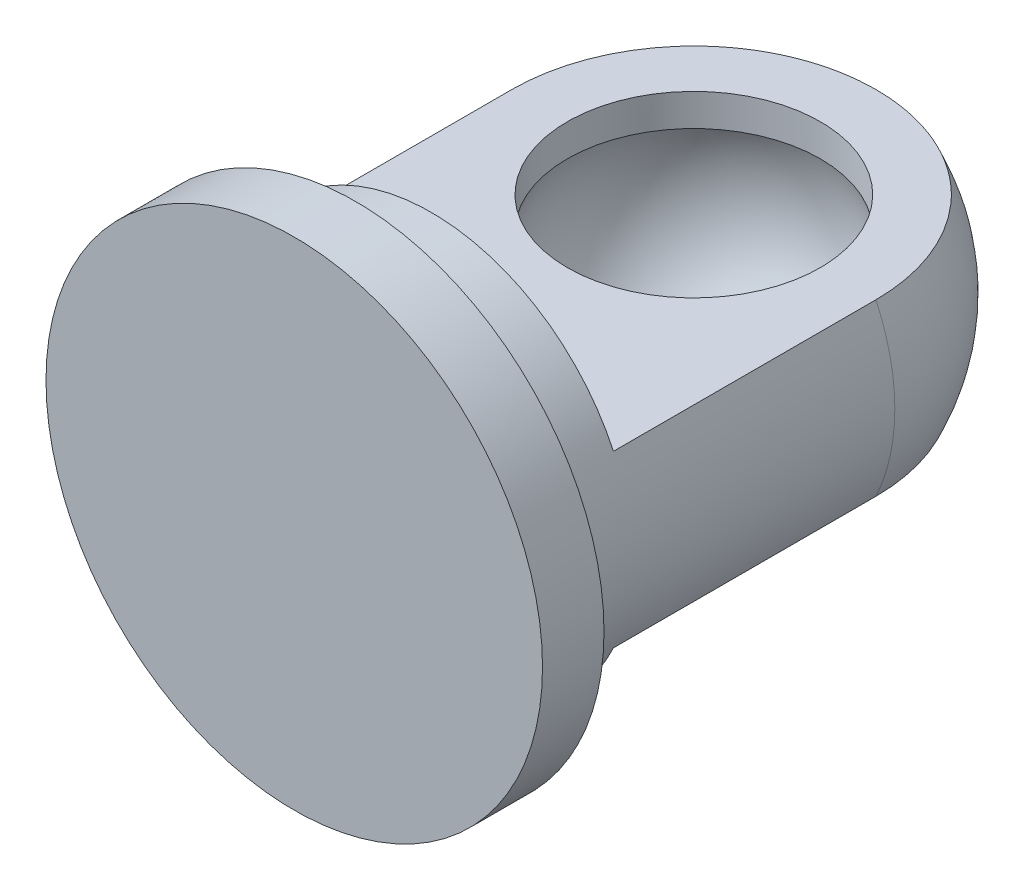
SolidWorks part; units mm, degrees
material "ABS"
ref_plane "Спереди" through (0, 0, 0) normal (0, 0, 1) x (1, 0, 0)
ref_plane "Сверху" through (0, 0, 0) normal (0, 1, 0) x (1, 0, 0)
ref_plane "Справа" through (0, 0, 0) normal (1, 0, 0) x (0, 0, -1)
sketch "Эскиз1" plane through (0, 0, 0) normal (0, 1, 0) x (1, 0, 0)
  line L1 (0, 0) -> (5.25, 0)
  line L2 (0, 0) -> (0, 1.3)
  line L3 (0, 1.3) -> (5.25, 1.3)
  line L4 (5.25, 0) -> (5.25, 1.3)
  line L5 (0, 1.3) -> (4.25, 1.3)
  line L6 (0, 1.3) -> (0, 12.7)
  line L7 (0, 12.7) -> (4.25, 12.7)
  line L8 (4.25, 1.3) -> (4.25, 12.7)
  circle A0 centre (0, 8.45) radius 4.25
  circle A1 centre (0, 8.45) radius 2.9
  dimension "D5" = 5.8
  dimension "D1" = 5.25
  dimension "D2" = 4.25
  dimension "D3" = 12.7
  dimension "D4" = 1.3
revolve "Повернуть1" add sketch "Эскиз1" angle 360 about L6 region at (2.625, 0, -0.65) region at (2.4063, 0, -3.3241) region at (0.095, 0, -4.875)
sketch "Эскиз2" plane through (0, 0, 0) normal (0, 0, 1) x (1, 0, 0)
  line L1 (-7.5, 1.8) -> (7.5, 1.8)
  line L2 (-7.5, 1.8) -> (-7.5, -1.8)
  line L3 (-7.5, -1.8) -> (7.5, -1.8)
  line L4 (7.5, 1.8) -> (7.5, -1.8)
  line L5 (-7.5, 1.8) -> (7.5, -1.8) construction
  line L6 (-7.5, -1.8) -> (7.5, 1.8) construction
  point P0 (0, 0)
  dimension "D1" = 3.6
  dimension "D2" = 15
extrude "Вырез-Вытянуть1" cut sketch "Эскиз2" against normal blind 10 from offset 2.9 flip side to cut offset against normal yes
sketch "Эскиз3" plane through (0, 1.8, 0) normal (0, 1, 0) x (1, 0, 0)
  circle A0 centre (0, 8.45) radius 2.675
  circle A1 centre (0, 8.45) radius 2.2738 construction
  dimension "D1" = 5.35
extrude "Вырез-Вытянуть2" cut sketch "Эскиз3" against normal up to next
